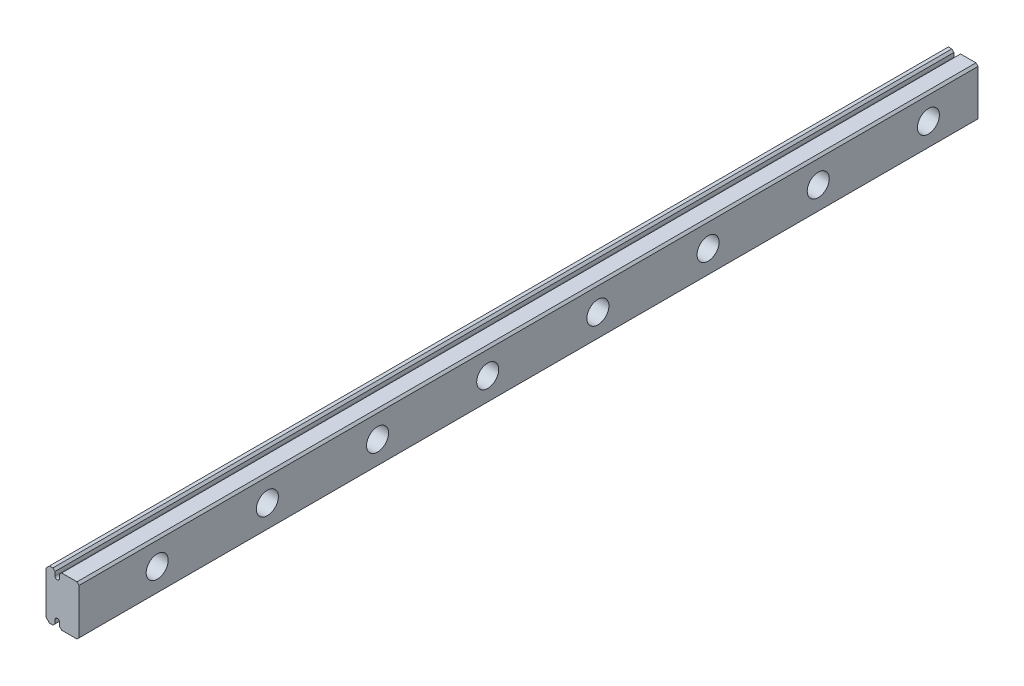
SolidWorks part; units mm, degrees
ref_plane "Front Plane" through (0, 0, 0) normal (0, 0, 1) x (1, 0, 0)
ref_plane "Top Plane" through (0, 0, 0) normal (0, 1, 0) x (1, 0, 0)
ref_plane "Right Plane" through (0, 0, 0) normal (1, 0, 0) x (0, 0, -1)
sketch "Sketch1" plane through (0, 0, 0) normal (0, 0, 1) x (1, 0, 0)
  line L0 (10.1686, -5.0147) -> (10.1684, 3.2353)
  line L1 (10.1684, 3.2353) -> (9.7934, 3.6103)
  line L2 (9.7934, 3.6103) -> (7.0059, 3.6102)
  line L3 (7.0059, 3.6102) -> (6.6309, 3.2352)
  line L4 (6.6309, 3.2352) -> (6.6309, 2.5477)
  line L5 (5.7934, 2.5477) -> (5.7934, 3.2352)
  line L6 (5.7934, 3.2352) -> (5.4184, 3.6102)
  line L7 (5.4184, 3.6102) -> (4.7934, 3.6101)
  line L8 (4.7934, 3.6101) -> (4.1684, 2.9851)
  line L9 (4.1684, 2.9851) -> (4.1686, -4.7649)
  line L10 (4.1686, -4.7649) -> (4.7936, -5.3899)
  line L11 (4.7936, -5.3899) -> (5.4186, -5.3898)
  line L12 (5.4186, -5.3898) -> (5.7936, -5.0148)
  line L13 (5.7936, -5.0148) -> (5.7936, -4.3273)
  line L14 (6.6311, -4.3273) -> (6.6311, -5.0148)
  line L15 (6.6311, -5.0148) -> (7.0061, -5.3898)
  line L16 (7.0061, -5.3898) -> (9.7936, -5.3897)
  line L17 (9.7936, -5.3897) -> (10.1686, -5.0147)
  arc A0 (6.2122, 2.1289) -> (6.6309, 2.5477) centre (6.2122, 2.5477) ccw
  arc A1 (5.7934, 2.5477) -> (6.2122, 2.1289) centre (6.2122, 2.5477) ccw
  arc A2 (6.6311, -4.3273) -> (5.7936, -4.3273) centre (6.2123, -4.3273) ccw
extrude "Boss-Extrude4" add sketch "Sketch1" along normal blind 200
sketch "Sketch3" plane through (4.1685, 0.0001, 0) normal (-1, 0, 0) x (0, 0, 1)
  line L0 (0, -0.89) -> (9, -0.89)
  line L1 (0, 2.985) -> (0, -4.765) construction
  circle A0 centre (9, -0.89) radius 2
  circle A1 centre (9, -0.89) radius 3
  circle A2 centre (29, -0.89) radius 3
  circle A3 centre (29, -0.89) radius 2
  circle A4 centre (49, -0.89) radius 3
  circle A5 centre (49, -0.89) radius 2
  circle A6 centre (69, -0.89) radius 3
  circle A7 centre (69, -0.89) radius 2
  circle A8 centre (89, -0.89) radius 3
  circle A9 centre (89, -0.89) radius 2
  circle A10 centre (109, -0.89) radius 3
  circle A11 centre (109, -0.89) radius 2
  circle A12 centre (129, -0.89) radius 3
  circle A13 centre (129, -0.89) radius 2
  circle A14 centre (149, -0.89) radius 3
  circle A15 centre (149, -0.89) radius 2
  circle A16 centre (169, -0.89) radius 3
  circle A17 centre (169, -0.89) radius 2
  circle A18 centre (189, -0.89) radius 3
  circle A19 centre (189, -0.89) radius 2
  dimension "D1" = 10
extrude "Cut-Extrude1" cut sketch "Sketch3" against normal blind 200 contours A0 | A3 | A5 | A7 | A9 | A11 | A19 | A17 | A15 | A13 region at (4.1684, 1.0536, 9) region at (4.1685, -0.8899, 29) region at (4.1685, -0.8899, 49) region at (4.1685, -0.8899, 69) region at (4.1685, -0.8899, 89) region at (4.1685, -0.8899, 109) region at (4.1685, -0.8899, 149) region at (4.1685, -0.8899, 169) region at (4.1685, -0.8899, 189)
extrude "Cut-Extrude2" cut sketch "Sketch3<3>" against normal blind 2.5 contours A1 A0 | A2 A3 | A4 A5 | A6 A7 | A8 A9 | A10 | A12 | A14 | A16 | A18 region at (4.1684, 2.0253, 9) region at (4.1685, -0.8899, 26.0849) region at (4.1685, -0.8899, 46.0849) region at (4.1685, -0.8899, 66.0849) region at (4.1685, -0.8899, 86.0849)
sketch "Sketch3<3>" plane through (4.1685, 0.0001, 0) normal (-1, 0, 0) x (0, 0, 1) same geometry as "Sketch3"
sketch "Sketch4" plane through (10.1685, 0.0003, 0) normal (1, 0, 0) x (0, 0, -1)
  line L0 (-200, -5.39) -> (0, -5.39) construction
  line L1 (-200, 3.61) -> (-163.1842, 3.61)
  line L2 (-200, 3.61) -> (-200, -5.39)
  line L3 (-200, -5.39) -> (-163.1842, -5.39)
  line L4 (-163.1842, 3.61) -> (-163.1842, -5.39)
extrude "Cut-Extrude3" cut sketch "Sketch4" against normal blind 10
